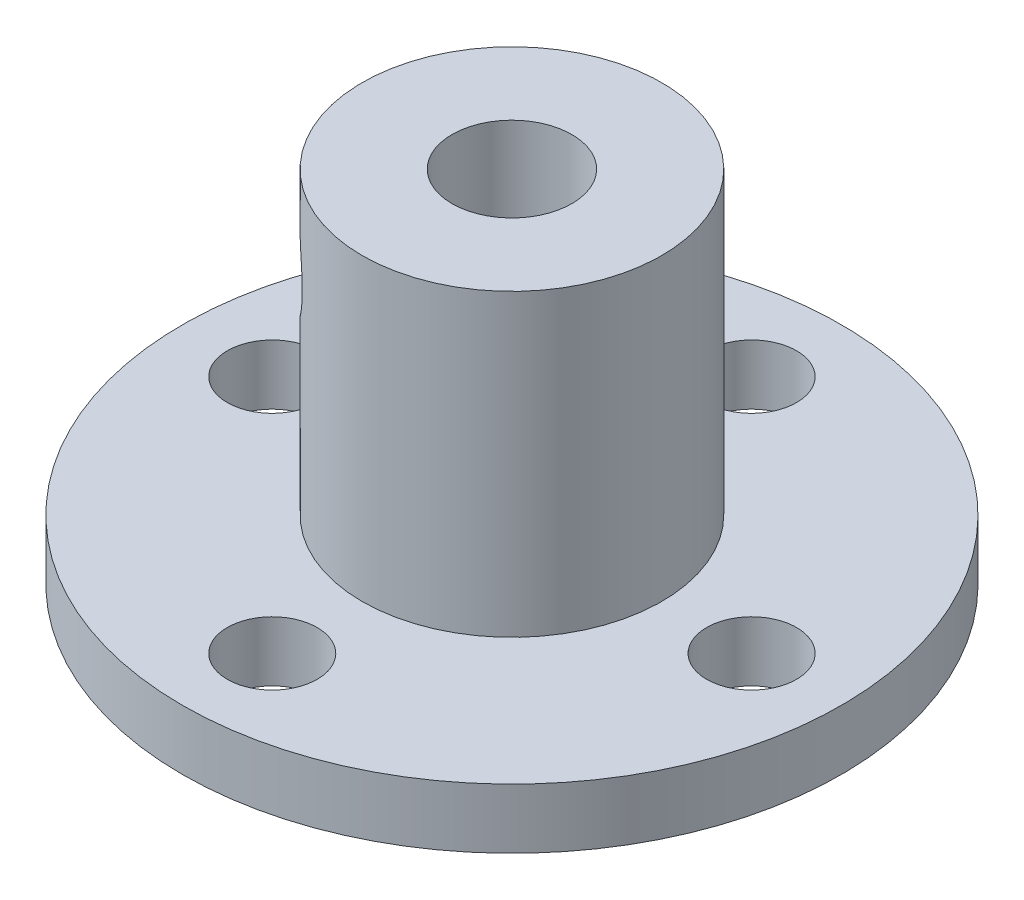
SolidWorks part; units mm, degrees
ref_plane "Front Plane" through (0, 0, 0) normal (0, 0, 1) x (1, 0, 0)
ref_plane "Top Plane" through (0, 0, 0) normal (0, 1, 0) x (1, 0, 0)
ref_plane "Right Plane" through (0, 0, 0) normal (1, 0, 0) x (0, 0, -1)
sketch "Sketch1" plane through (0, 0, 0) normal (0, 1, 0) x (1, 0, 0)
  line L0 (0, 0) -> (0, 8) construction
  circle A0 centre (0, 0) radius 11
  circle A1 centre (0, 0) radius 2
  circle A2 centre (0, 0) radius 5
  circle A3 centre (0, 8) radius 1.5
  circle A4 centre (8, 0) radius 1.5
  circle A5 centre (0, -8) radius 1.5
  circle A6 centre (-8, 0) radius 1.5
  point P5 (0, 8)
  dimension "D1" = 4
  dimension "D2" = 22
  dimension "D3" = 10
  dimension "D5" = 3
  dimension "D4" = 8
  dimension "D6" = 4
extrude "Boss-Extrude1" add sketch "Sketch1" along normal blind 2 contours A0 A6 A5 A4 A2 A3 region at (-10.6889, 0, 0)
extrude "Boss-Extrude2" add sketch "Sketch1<3>" along normal blind 12 contours A1 A2 region at (-4.8586, 0, 0)
sketch "Sketch1<3>" plane through (0, 0, 0) normal (0, 1, 0) x (1, 0, 0) same geometry as "Sketch1"
ref_plane "Plane2" through (-4.0625, 0, 2.9148) normal (-0.8125, 0, 0.583) x (0.583, 0, 0.8125)
sketch "Sketch2" plane through (-4.0625, 0, 2.9148) normal (-0.8125, 0, 0.583) x (0.583, 0, 0.8125)
  line L0 (5, 2) -> (-5, 2) construction
  circle A0 centre (0, 9) radius 1.5
  dimension "D2" = 3
  dimension "D1" = 7
extrude "Cut-Extrude1" cut sketch "Sketch2" against normal up to surface (3.6771 mm away) up to face at (0, 12, 2)
